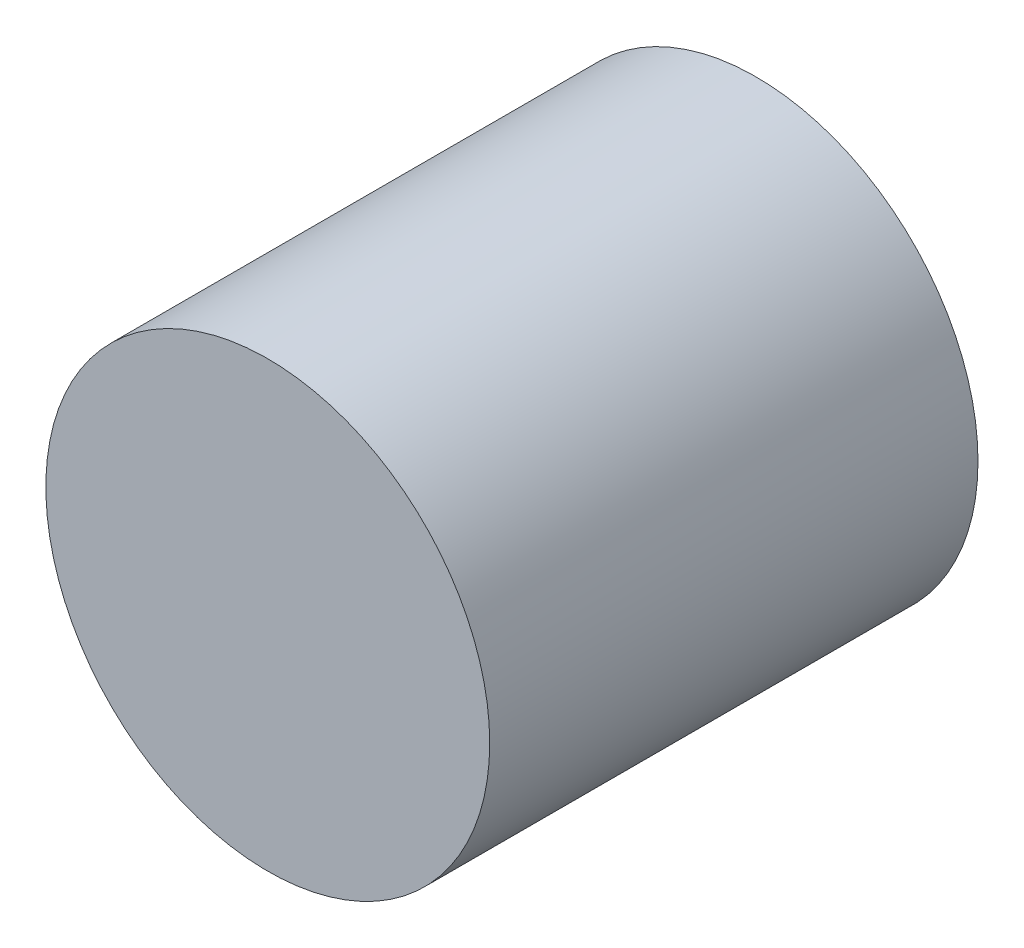
SolidWorks part; units mm, degrees
ref_plane "Front Plane" through (0, 0, 0) normal (0, 0, 1) x (1, 0, 0)
ref_plane "Top Plane" through (0, 0, 0) normal (0, 1, 0) x (1, 0, 0)
ref_plane "Right Plane" through (0, 0, 0) normal (1, 0, 0) x (0, 0, -1)
sketch "Sketch1" plane through (0, 0, 0) normal (0, 0, 1) x (1, 0, 0)
  line L0 (-64.4613, 54.2738) -> (-64.4613, -54.2738)
  line L1 (-62.4613, 52.2738) -> (62.4613, 52.2738)
  line L2 (-62.4613, 52.2738) -> (-62.4613, -52.2738)
  line L3 (-62.4613, -52.2738) -> (62.4613, -52.2738)
  line L4 (62.4613, 52.2738) -> (62.4613, -52.2738)
  line L5 (-62.4613, 52.2738) -> (62.4613, -52.2738) construction
  line L6 (-62.4613, -52.2738) -> (62.4613, 52.2738) construction
  line L7 (-64.4613, -54.2738) -> (64.4613, -54.2738)
  line L8 (64.4613, 54.2738) -> (64.4613, -54.2738)
  line L9 (-64.4613, 54.2738) -> (64.4613, 54.2738)
  point P0 (0, 0)
  dimension "D1" = 2
extrude "Boss-Extrude1" add sketch "Sketch1" along normal blind 50
sketch "Sketch2" plane through (0, 0, 0) normal (0, 0, 1) x (1, 0, 0)
  circle A0 centre (0, 0) radius 50
  dimension "D1" = 100
extrude "Boss-Extrude2" add sketch "Sketch2" along normal blind 110 separate body
sketch "Sketch3" plane through (0, 0, 0) normal (0, 0, 1) x (1, 0, 0)
  circle A0 centre (-51.1264, 41.5168) radius 6.9941
  circle A1 centre (46.4615, 43.756) radius 6.1207
extrude "Boss-Extrude3" add sketch "Sketch3" along normal blind 20 separate body
delete or keep bodies "Body-Delete1" type delete bodies bodies 104 103 101
